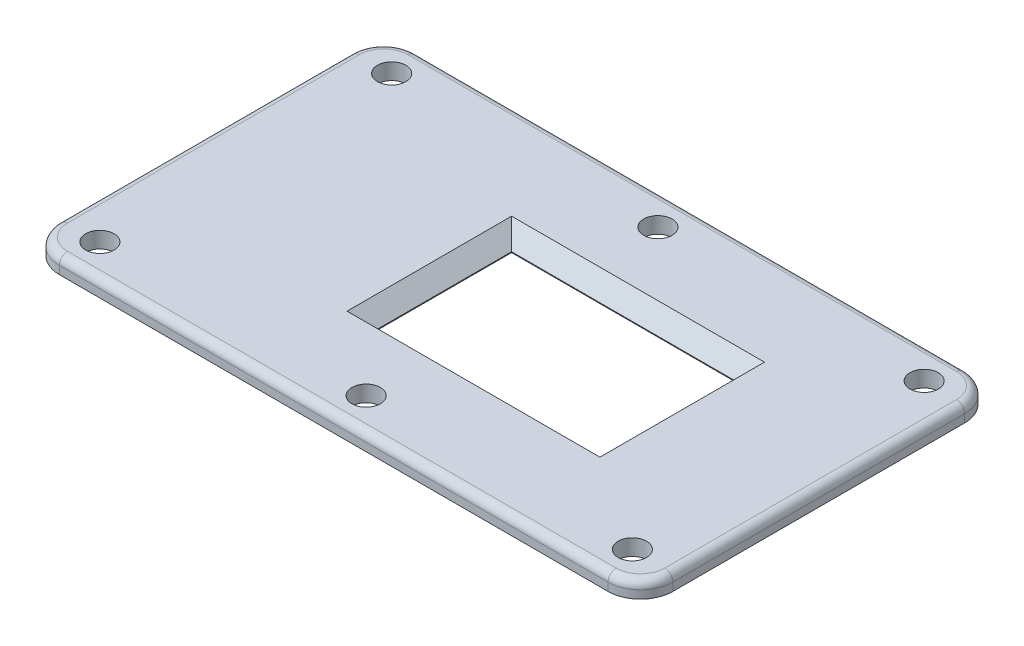
SolidWorks part; units mm, degrees
ref_plane "Front Plane" through (0, 0, 0) normal (0, 0, 1) x (1, 0, 0)
ref_plane "Top Plane" through (0, 0, 0) normal (0, 1, 0) x (1, 0, 0)
ref_plane "Right Plane" through (0, 0, 0) normal (1, 0, 0) x (0, 0, -1)
sketch "Sketch1" plane through (0, 0, 0) normal (0, 1, 0) x (1, 0, 0)
  line L1 (-13.7, -8.25) -> (13.7, -8.25)
  line L2 (-13.7, -8.25) -> (-13.7, 8.25)
  line L3 (-13.7, 8.25) -> (13.7, 8.25)
  line L4 (13.7, -8.25) -> (13.7, 8.25)
  line L5 (-13.7, -8.25) -> (13.7, 8.25) construction
  line L6 (-13.7, 8.25) -> (13.7, -8.25) construction
  line L7 (-15.75, 10.25) -> (15.75, 10.25)
  line L8 (-15.75, 10.25) -> (-15.75, -10.25)
  line L9 (-15.75, -10.25) -> (15.75, -10.25)
  line L10 (15.75, 10.25) -> (15.75, -10.25)
  line L11 (-15.75, 10.25) -> (15.75, -10.25) construction
  line L12 (-15.75, -10.25) -> (15.75, 10.25) construction
  line L13 (-33.25, 13) -> (22.45, 13)
  line L14 (-33.25, 13) -> (-33.25, -13)
  line L15 (-33.25, -13) -> (22.45, -13)
  line L16 (22.45, 13) -> (22.45, -13)
  line L20 (-5.4, 13) -> (-5.4, 28.3625) construction
  line L21 (-33.25, 0) -> (-43.25, 0) construction
  line L23 (-39.25, 22) -> (28.45, 22)
  line L24 (-43.25, 18) -> (-43.25, -18)
  line L25 (-39.25, -22) -> (28.45, -22)
  line L26 (32.45, 18) -> (32.45, -18)
  circle A0 centre (-5.4, 18) radius 1.75
  circle A1 centre (-38.25, 18) radius 1.75
  circle A2 centre (27.45, 18) radius 1.75
  circle A3 centre (27.45, -18) radius 1.75
  circle A4 centre (-5.4, -18) radius 1.75
  circle A5 centre (-38.25, -18) radius 1.75
  arc A6 (-43.25, -18) -> (-39.25, -22) centre (-39.25, -18) ccw
  arc A7 (28.45, -22) -> (32.45, -18) centre (28.45, -18) ccw
  arc A8 (28.45, 22) -> (32.45, 18) centre (28.45, 18) cw
  arc A9 (-39.25, 22) -> (-43.25, 18) centre (-39.25, 18) ccw
  point P0 (0, 0)
  point P5 (0, 0)
  point P15 (-33.25, 0)
  point P24 (-43.25, 0)
  dimension "D8" = 3.5
  dimension "D9" = 3.5
  dimension "D10" = 5
  dimension "D11" = 5
  dimension "D12" = 5
  dimension "D13" = 5
  dimension "D14" = 4
  dimension "D15" = 4
  dimension "D1" = 16.5
  dimension "D2" = 27.4
  dimension "D3" = 20.5
  dimension "D4" = 31.5
  dimension "D5" = 8.75
  dimension "D6" = 26
  dimension "D7" = 17.5
extrude "Boss-Extrude1" add sketch "Sketch1" along normal blind 2 contours L23 A9 L24 A6 L25 A7 L26 A8 A5 A2 A1 A0 L13 L16 L15 L14 A3 A4 | L16 L13 L14 L15 L7 L10 L9 L8 | L10 L7 L8 L9 L4 L1 L2 L3 region at (0, 0, -9.8742) region at (-5.4, 0, -12.3853) region at (-5.4, 0, -21.1244)
extrude "Boss-Extrude2" add sketch "Sketch1<3>" along normal blind 1 contours L10 L7 L8 L9 L4 L1 L2 L3 region at (0, 0, -9.8742)
sketch "Sketch1<3>" plane through (0, 0, 0) normal (0, 1, 0) x (1, 0, 0) same geometry as "Sketch1"
fillet "Fillet1" radius 1 8 edges at (-42.0784, 2, 20.8284) (-43.25, 2, 0) (-42.0784, 2, -20.8284) (-5.4, 2, -22) (31.2784, 2, -20.8284) (32.45, 2, 0) (31.2784, 2, 20.8284) (-5.4, 2, 22)
chamfer "Chamfer1" distance 1.9 angle 45 4 edges at (-13.7, 2, 0) (0, 2, 8.25) (13.7, 2, 0) (0, 2, -8.25)
